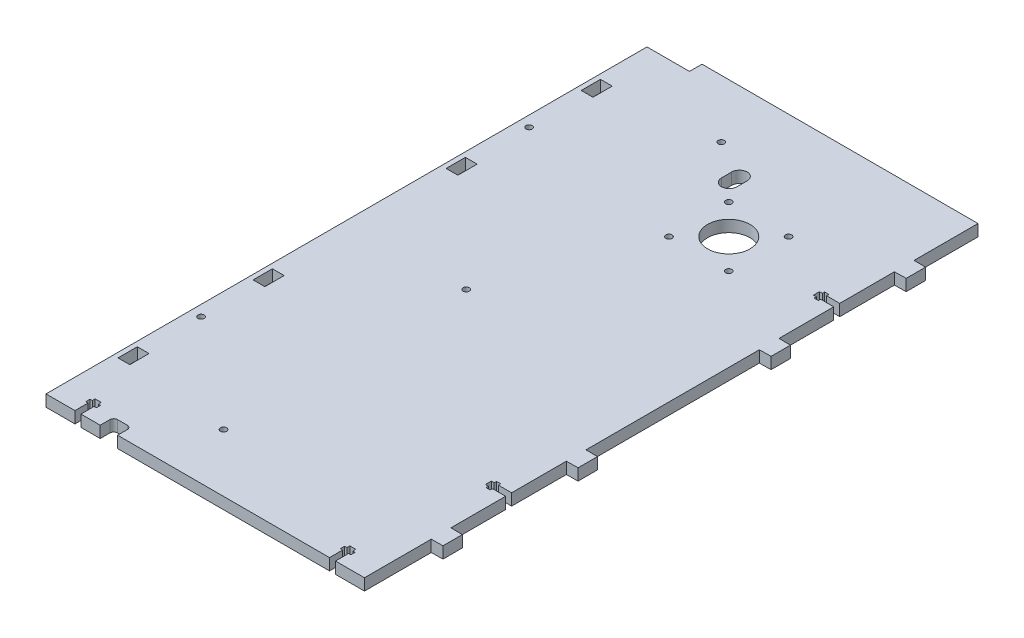
SolidWorks part; units mm, degrees
material "Клен"
ref_plane "Front" through (0, 0, 0) normal (0, 0, 1) x (1, 0, 0)
ref_plane "Top" through (0, 0, 0) normal (0, 1, 0) x (1, 0, 0)
ref_plane "Right" through (0, 0, 0) normal (1, 0, 0) x (0, 0, -1)
sketch "Эскиз1" plane through (0, 0, 6) normal (0, 1, 0) x (1, 0, 0)
  line L0 (830.1555, 858.9465) -> (830.1555, 507.3335) construction
  line L1 (746.0135, 673.4222) -> (945.6578, 673.4222) construction
  line L2 (746.0135, 805.6234) -> (945.6578, 805.6234) construction
  line L3 (746.0135, 547.7211) -> (945.6578, 547.7211) construction
  line L4 (883.1555, 853.0128) -> (883.1555, 710.7402) construction
  line L7 (846.2247, 794.9498) -> (846.2247, 789.6669)
  line L8 (854.2247, 789.6669) -> (854.2247, 794.9498)
  line L16 (776.7555, 552.5234) -> (776.7555, 562.5234)
  line L17 (770.6555, 562.5234) -> (770.6555, 552.5234)
  line L18 (770.6555, 552.5234) -> (776.7555, 552.5234)
  line L19 (776.7555, 562.5234) -> (770.6555, 562.5234)
  line L20 (770.6555, 622.5234) -> (776.7555, 622.5234)
  line L21 (776.7555, 622.5234) -> (776.7555, 632.5234)
  line L22 (776.7555, 632.5234) -> (770.6555, 632.5234)
  line L23 (770.6555, 632.5234) -> (770.6555, 622.5234)
  line L24 (776.7555, 722.5234) -> (776.7555, 732.5234)
  line L25 (770.6555, 722.5234) -> (776.7555, 722.5234)
  line L26 (770.6555, 732.5234) -> (770.6555, 722.5234)
  line L27 (776.7555, 732.5234) -> (770.6555, 732.5234)
  line L28 (770.6555, 792.5234) -> (776.7555, 792.5234)
  line L29 (776.7555, 792.5234) -> (776.7555, 802.5234)
  line L30 (776.7555, 802.5234) -> (770.6555, 802.5234)
  line L31 (770.6555, 802.5234) -> (770.6555, 792.5234)
  line L32 (833.1555, 858.9465) -> (833.1555, 507.3335) construction
  line L33 (933.1555, 858.9465) -> (933.1555, 507.3335) construction
  line L34 (933.1555, 517.7211) -> (933.1555, 552.3234)
  line L35 (933.1555, 593.9734) -> (933.1555, 622.3234)
  line L36 (933.1555, 622.3234) -> (939.1555, 622.4234)
  line L37 (924.1555, 589.6734) -> (924.1555, 590.8734)
  line L38 (939.1555, 722.4234) -> (939.1555, 732.4234)
  line L39 (939.1555, 562.4234) -> (933.1555, 562.5234)
  line L40 (924.1555, 765.1734) -> (926.3555, 765.1734)
  line L41 (933.1555, 562.5234) -> (933.1555, 590.8734)
  line L42 (926.3555, 589.6734) -> (924.1555, 589.6734)
  line L43 (922.6555, 760.8734) -> (922.6555, 763.9734)
  line L44 (926.3555, 759.6734) -> (924.1555, 759.6734)
  line L45 (933.1555, 763.9734) -> (933.1555, 792.3234)
  line L46 (926.3555, 595.1734) -> (926.3555, 593.9734)
  line L47 (926.3555, 760.8734) -> (926.3555, 759.6734)
  line L48 (939.1555, 622.4234) -> (939.1555, 632.4234)
  line L49 (939.1555, 732.4234) -> (933.1555, 732.5234)
  line L50 (926.3555, 763.9734) -> (933.1555, 763.9734)
  line L51 (926.3555, 593.9734) -> (933.1555, 593.9734)
  line L52 (924.1555, 760.8734) -> (922.6555, 760.8734)
  line L53 (933.1555, 590.8734) -> (926.3555, 590.8734)
  line L54 (933.1555, 632.5234) -> (933.1555, 722.3234)
  line L55 (924.1555, 763.9734) -> (924.1555, 765.1734)
  line L56 (933.1555, 802.5234) -> (933.1555, 835.6234)
  line L57 (924.1555, 590.8734) -> (922.6555, 590.8734)
  line L58 (924.1555, 595.1734) -> (926.3555, 595.1734)
  line L59 (933.1555, 792.3234) -> (939.1555, 792.4234)
  line L60 (933.1555, 760.8734) -> (926.3555, 760.8734)
  line L61 (922.6555, 763.9734) -> (924.1555, 763.9734)
  line L124 (805.2555, 522.7211) -> (805.2555, 517.7211)
  line L125 (805.2555, 517.7211) -> (833.1555, 517.7211)
  line L167 (833.1555, 835.6234) -> (790.1555, 835.6234)
  line L168 (790.1555, 835.6234) -> (790.1555, 829.1234)
  line L169 (790.1555, 829.1234) -> (768.1555, 829.1234)
  line L170 (768.1555, 829.1234) -> (768.1555, 517.7211)
  line L171 (768.1555, 517.7211) -> (783.1555, 517.7211)
  line L172 (783.1555, 517.7211) -> (783.1555, 524.5211)
  line L173 (783.1555, 524.5211) -> (781.9555, 524.5211)
  line L174 (781.9555, 524.5211) -> (781.9555, 526.7211)
  line L175 (781.9555, 526.7211) -> (783.1555, 526.7211)
  line L176 (783.1555, 526.7211) -> (783.1555, 528.2211)
  line L177 (783.1555, 528.2211) -> (786.2555, 528.2211)
  line L178 (786.2555, 528.2211) -> (786.2555, 526.7211)
  line L179 (786.2555, 526.7211) -> (787.4555, 526.7211)
  line L180 (787.4555, 526.7211) -> (787.4555, 524.5211)
  line L181 (787.4555, 524.5211) -> (786.2555, 524.5211)
  line L182 (786.2555, 524.5211) -> (786.2555, 517.7211)
  line L183 (786.2555, 517.7211) -> (796.2555, 517.7211)
  line L184 (796.2555, 517.7211) -> (796.2555, 522.7211)
  line L185 (798.2555, 524.7211) -> (803.2555, 524.7211)
  line L186 (926.3555, 590.8734) -> (926.3555, 589.6734)
  line L187 (939.1555, 632.4234) -> (933.1555, 632.5234)
  line L188 (933.1555, 552.3234) -> (939.1555, 552.4234)
  line L189 (922.6555, 590.8734) -> (922.6555, 593.9734)
  line L190 (933.1555, 722.3234) -> (939.1555, 722.4234)
  line L191 (933.1555, 732.5234) -> (933.1555, 760.8734)
  line L192 (924.1555, 593.9734) -> (924.1555, 595.1734)
  line L193 (924.1555, 759.6734) -> (924.1555, 760.8734)
  line L194 (926.3555, 765.1734) -> (926.3555, 763.9734)
  line L195 (939.1555, 802.4234) -> (933.1555, 802.5234)
  line L196 (939.1555, 552.4234) -> (939.1555, 562.4234)
  line L197 (922.6555, 593.9734) -> (924.1555, 593.9734)
  line L198 (939.1555, 792.4234) -> (939.1555, 802.4234)
  line L199 (833.1555, 835.6234) -> (933.1555, 835.6234)
  line L200 (933.1555, 517.7211) -> (918.1555, 517.7211)
  line L201 (915.0555, 517.7211) -> (915.0555, 524.5211)
  line L202 (913.8555, 526.7211) -> (915.0555, 526.7211)
  line L203 (919.3555, 524.5211) -> (918.1555, 524.5211)
  line L204 (915.0555, 524.5211) -> (913.8555, 524.5211)
  line L205 (918.1555, 526.7211) -> (919.3555, 526.7211)
  line L206 (918.1555, 524.5211) -> (918.1555, 517.7211)
  line L207 (915.0555, 526.7211) -> (915.0555, 528.2211)
  line L208 (913.8555, 524.5211) -> (913.8555, 526.7211)
  line L209 (918.1555, 528.2211) -> (918.1555, 526.7211)
  line L210 (915.0555, 528.2211) -> (918.1555, 528.2211)
  line L211 (919.3555, 526.7211) -> (919.3555, 524.5211)
  line L212 (915.0555, 517.7211) -> (833.1555, 517.7211)
  circle A0 centre (830.1555, 805.6234) radius 1.6
  circle A1 centre (830.1555, 673.4222) radius 1.6
  circle A2 centre (830.1555, 547.7211) radius 1.6
  circle A3 centre (858.9752, 780.6734) radius 1.6
  arc A4 (805.2555, 522.7211) -> (803.2555, 524.7211) centre (803.2555, 522.7211) ccw
  arc A5 (798.2555, 524.7211) -> (796.2555, 522.7211) centre (798.2555, 522.7211) ccw
  circle A6 centre (773.7055, 592.5234) radius 1.6
  circle A7 centre (773.7055, 762.5234) radius 1.6
  circle A8 centre (858.9752, 749.6734) radius 1.6
  circle A9 centre (874.4752, 765.1734) radius 11
  circle A10 centre (889.9752, 749.6734) radius 1.6
  circle A11 centre (889.9752, 780.6734) radius 1.6
  arc A14 (846.2247, 789.6669) -> (854.2247, 789.6669) centre (850.2247, 789.6669) ccw
  arc A15 (854.2247, 794.9498) -> (846.2247, 794.9498) centre (850.2247, 794.9498) ccw
  dimension "D7" = 3.2
  dimension "D8" = 3.2
  dimension "D9" = 3.2
  dimension "D2" = 100
  dimension "D3" = 15
  dimension "D4" = 30
  dimension "D1" = 3
  dimension "D5" = 30
  dimension "D6" = 162.2012
  dimension "D10" = 50
extrude "Бобышка-Вытянуть1" add sketch "Эскиз1" against normal blind 6
